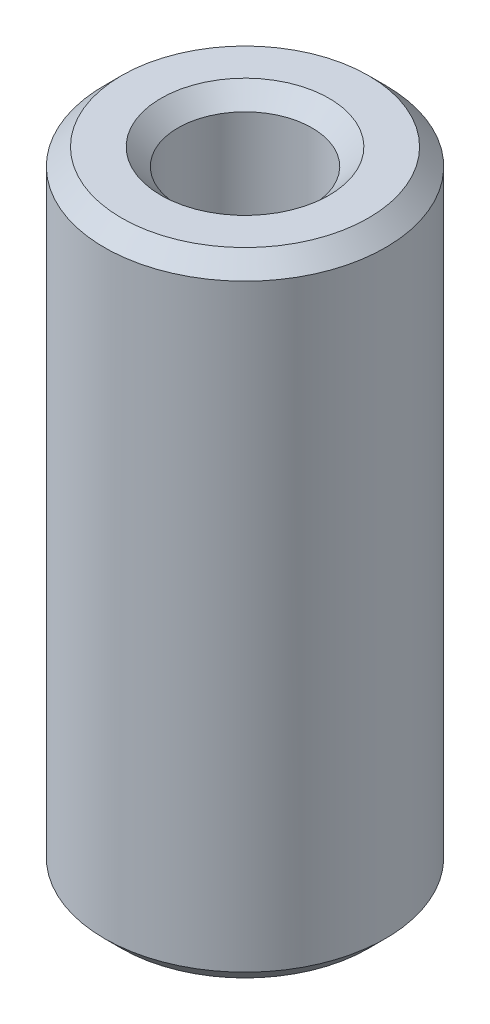
SolidWorks part; units mm, degrees
ref_plane "Front Plane" through (0, 0, 0) normal (0, 0, 1) x (1, 0, 0)
ref_plane "Top Plane" through (0, 0, 0) normal (0, 1, 0) x (1, 0, 0)
ref_plane "Right Plane" through (0, 0, 0) normal (1, 0, 0) x (0, 0, -1)
sketch "Sketch1" plane through (0, 0, 0) normal (0, 1, 0) x (1, 0, 0)
  circle A0 centre (0, 0) radius 7.5
  dimension "SLEEVE_OD" = 15
extrude "Boss-Extrude1" add sketch "Sketch1" along normal blind 33.7643
sketch "Sketch2" plane through (0, 0, 0) normal (0, 1, 0) x (1, 0, 0)
  circle A0 centre (0, 0) radius 3.5762
  dimension "BORE_D" = 7.1525
extrude "Cut-Extrude1" cut sketch "Sketch2" along normal through all
chamfer "Chamfer1" distance 0.9113 angle 45 4 edges at (0, 33.7643, 3.5762) (0, 0, 3.5762) (0, 0, 7.5) (0, 33.7643, 7.5)
